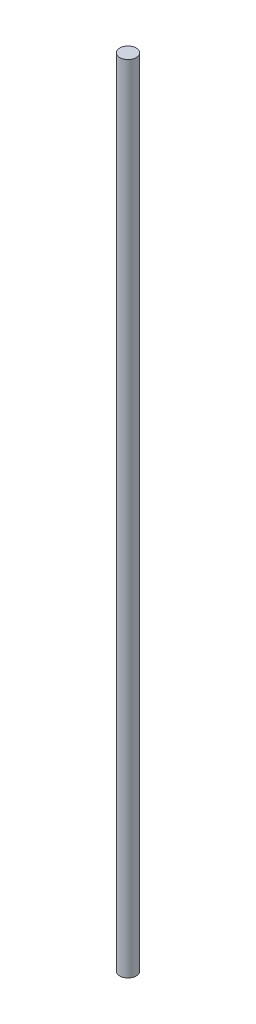
SolidWorks part; units mm, degrees
ref_plane "Front Plane" through (0, 0, 0) normal (0, 0, 1) x (1, 0, 0)
ref_plane "Top Plane" through (0, 0, 0) normal (0, 1, 0) x (1, 0, 0)
ref_plane "Right Plane" through (0, 0, 0) normal (1, 0, 0) x (0, 0, -1)
sketch "Sketch1" plane through (0, 0, 0) normal (0, 1, 0) x (1, 0, 0)
  circle A0 centre (0, 0) radius 6.35
  dimension "D1" = 12.7
extrude "Boss-Extrude1" add sketch "Sketch1" along normal mid plane 609.6
